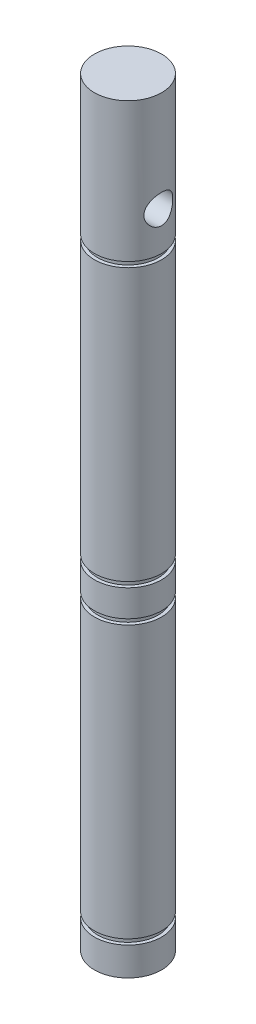
SolidWorks part; units mm, degrees
ref_plane "Front Plane" through (0, 0, 0) normal (0, 0, 1) x (1, 0, 0)
ref_plane "Top Plane" through (0, 0, 0) normal (0, 1, 0) x (1, 0, 0)
ref_plane "Right Plane" through (0, 0, 0) normal (1, 0, 0) x (0, 0, -1)
sketch "Sketch1" plane through (0, 0, 0) normal (0, 1, 0) x (1, 0, 0)
  circle A0 centre (0, 0) radius 5
  dimension "D1" = 10
extrude "Boss-Extrude1" add sketch "Sketch1" along normal blind 113.2
sketch "Sketch2" plane through (0, 0, 0) normal (0, -1, 0) x (1, 0, 0)
  circle A0 centre (0, 0) radius 4.5
  circle A1 centre (0, 0) radius 5 construction
  circle A2 centre (0, 0) radius 5
  dimension "D1" = 0.5
extrude "Cut-Extrude2" cut sketch "Sketch2" against normal blind 0.8 from offset 4.25 offset against normal yes
extrude "Cut-Extrude3" cut sketch "Sketch2<2>" against normal blind 0.8 from offset 45.55 offset against normal yes
sketch "Sketch2<2>" plane through (0, 0, 0) normal (0, -1, 0) x (1, 0, 0) same geometry as "Sketch2"
extrude "Cut-Extrude4" cut sketch "Sketch2<3>" against normal blind 0.8 from offset 50.35 offset against normal yes
sketch "Sketch2<3>" plane through (0, 0, 0) normal (0, -1, 0) x (1, 0, 0) same geometry as "Sketch2"
extrude "Cut-Extrude5" cut sketch "Sketch2<4>" against normal blind 0.8 from offset 91.65 offset against normal yes
sketch "Sketch2<4>" plane through (0, 0, 0) normal (0, -1, 0) x (1, 0, 0) same geometry as "Sketch2"
sketch "Sketch3" plane through (0, 113.2, 0) normal (0, 1, 0) x (1, 0, 0)
  circle A0 centre (0, 0) radius 5
  circle A1 centre (0, 0) radius 5
  dimension "D1" = 10
  dimension "D2" = 10
ref_plane "Plane1" through (-5, 0, 0) normal (-1, 0, 0) x (0, 0, 1)
sketch "Sketch4" plane through (-5, 0, 0) normal (1, 0, 0) x (0, 0, -1)
  line L0 (5, 113.2) -> (-5, 113.2) construction
  line L1 (-5, 113.2) -> (-5, 92.45) construction
  circle A0 centre (0, 98.2) radius 1.5
  dimension "D2" = 3
  dimension "D1" = 15
  dimension "D3" = 5
extrude "Cut-Extrude6" cut sketch "Sketch4" along normal through all
hole_wizard "M4 Clearance Hole1" positions "Sketch10" profile "Sketch11" hole size "M4" standard "ANSI Metric" end condition through all
sketch "Sketch10" plane through (-5, 0, 0) normal (-1, 0, 0) x (0, 0, 1)
  point P0 (0, 98.2)
sketch "Sketch11" plane through (-5, 98.2, 0) normal (0, 1, 0) x (0, 0, 1)
  line L0 (0, 0) -> (0, 10)
  line L1 (0, 10) -> (2.15, 10)
  line L2 (2.15, 10) -> (2.15, 0)
  line L5 (2.15, 0) -> (0, 0)
  line L11 (0, -6.35) -> (0, 107.95) construction
  dimension "Thru Hole Dia." = 4.3
  dimension "Thru Hole Depth" = 10
